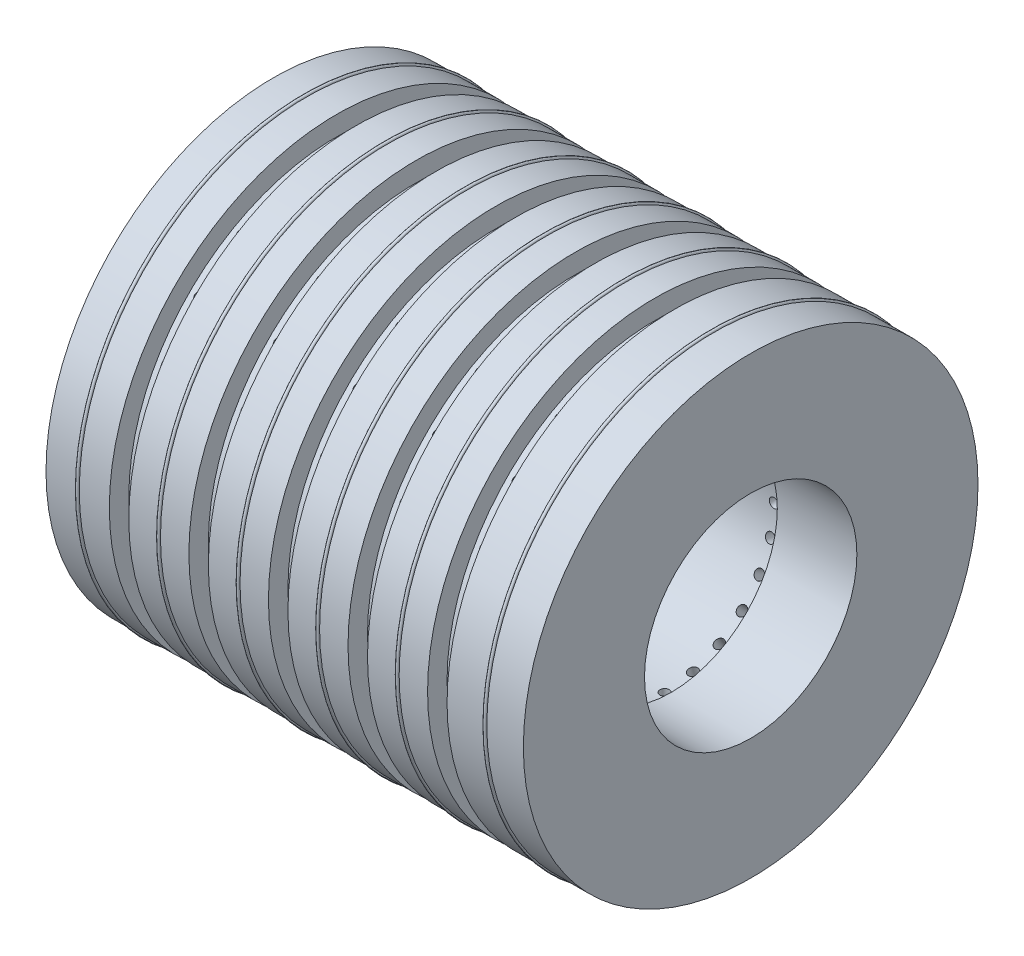
SolidWorks part; units mm, degrees
ref_plane "Front Plane" through (0, 0, 0) normal (0, 0, 1) x (1, 0, 0)
ref_plane "Top Plane" through (0, 0, 0) normal (0, 1, 0) x (1, 0, 0)
ref_plane "Right Plane" through (0, 0, 0) normal (1, 0, 0) x (0, 0, -1)
sketch "Sketch1" plane through (0, 0, 0) normal (0, 0, 1) x (1, 0, 0)
  line L0 (0, 0) -> (36.5459, 0) construction
  line L1 (-6.223, 9.5758) -> (-6.223, 17.78)
  line L3 (31.115, 17.78) -> (31.115, 8.3058)
  line L4 (31.115, 8.3058) -> (24.892, 8.3058)
  line L5 (24.892, 8.3058) -> (24.892, 8.5598)
  line L6 (24.892, 8.5598) -> (18.669, 8.5598)
  line L7 (18.669, 8.5598) -> (18.669, 8.8138)
  line L8 (18.669, 8.8138) -> (12.446, 8.8138)
  line L9 (12.446, 8.8138) -> (12.446, 9.0678)
  line L10 (12.446, 9.0678) -> (6.223, 9.0678)
  line L11 (6.223, 9.0678) -> (6.223, 9.3218)
  line L12 (6.223, 9.3218) -> (0, 9.3218)
  line L13 (0, 9.3218) -> (0, 9.5758)
  line L14 (0, 9.5758) -> (-6.223, 9.5758)
  line L15 (-6.223, 17.78) -> (-3.8735, 17.78)
  line L16 (-1.27, 17.78) -> (-1.27, 16.256)
  line L17 (-1.27, 16.256) -> (0.254, 16.256)
  line L18 (0.254, 16.256) -> (0.254, 17.78)
  line L19 (0.254, 17.78) -> (2.4765, 17.78)
  line L20 (4.953, 17.78) -> (4.953, 16.256)
  line L21 (4.953, 16.256) -> (6.477, 16.256)
  line L22 (6.477, 16.256) -> (6.477, 17.78)
  line L23 (6.477, 17.78) -> (8.6995, 17.78)
  line L24 (11.176, 17.78) -> (11.176, 16.256)
  line L25 (11.176, 16.256) -> (12.7, 16.256)
  line L26 (12.7, 16.256) -> (12.7, 17.78)
  line L27 (12.7, 17.78) -> (14.9225, 17.78)
  line L28 (17.399, 17.78) -> (17.399, 16.256)
  line L29 (17.399, 16.256) -> (18.923, 16.256)
  line L30 (18.923, 16.256) -> (18.923, 17.78)
  line L31 (18.923, 17.78) -> (21.1455, 17.78)
  line L32 (23.622, 17.78) -> (23.622, 16.256)
  line L33 (23.622, 16.256) -> (25.146, 16.256)
  line L34 (25.146, 16.256) -> (25.146, 17.78)
  line L35 (25.146, 17.78) -> (28.0035, 17.78)
  line L36 (-3.6195, 17.78) -> (-1.27, 17.78)
  line L37 (2.7305, 17.78) -> (4.953, 17.78)
  line L38 (8.9535, 17.78) -> (11.176, 17.78)
  line L39 (15.1765, 17.78) -> (17.399, 17.78)
  line L40 (21.3995, 17.78) -> (23.622, 17.78)
  line L41 (28.2575, 17.78) -> (31.115, 17.78)
  line L42 (-3.8735, 17.78) -> (-3.6195, 17.78) construction
  line L43 (2.4765, 17.78) -> (2.7305, 17.78) construction
  line L44 (8.6995, 17.78) -> (8.9535, 17.78) construction
  line L45 (14.9225, 17.78) -> (15.1765, 17.78) construction
  line L46 (21.1455, 17.78) -> (21.3995, 17.78) construction
  line L47 (28.0035, 17.78) -> (28.2575, 17.78) construction
  arc A9 (21.3995, 17.78) -> (21.1455, 17.78) centre (21.2725, 17.78) ccw
  arc A10 (15.1765, 17.78) -> (14.9225, 17.78) centre (15.0495, 17.78) ccw
  arc A11 (8.9535, 17.78) -> (8.6995, 17.78) centre (8.8265, 17.78) ccw
  arc A12 (2.7305, 17.78) -> (2.4765, 17.78) centre (2.6035, 17.78) ccw
  arc A13 (-3.6195, 17.78) -> (-3.8735, 17.78) centre (-3.7465, 17.78) ccw
  arc A14 (28.2575, 17.78) -> (28.0035, 17.78) centre (28.1305, 17.78) ccw
  point P37 (-6.223, 13.6779)
  dimension "D13" = 0.254
  dimension "D2" = 0.254
  dimension "D4" = 17.78
  dimension "D5" = 1.524
  dimension "D6" = 1.524
  dimension "D8" = 1.524
  dimension "D9" = 1.524
  dimension "D10" = 1.524
  dimension "D11" = 1.524
  dimension "D3" = 6.223
  dimension "D12" = 37.338
  dimension "D14" = 9.5758
  dimension "D7" = 0.254
  dimension "D15" = 0.254
  dimension "D16" = 0.254
  dimension "D17" = 0.254
  dimension "D18" = 0.254
revolve "Revolve1" add sketch "Sketch1" angle 360 about L0
ref_plane "Plane1" through (-0.508, 0, 0) normal (-1, 0, 0) x (0, 0, 1)
ref_plane "Plane2" through (5.715, 0, 0) normal (-1, 0, 0) x (0, 0, 1)
ref_plane "Plane3" through (11.938, 0, 0) normal (1, 0, 0) x (0, 0, -1)
ref_plane "Plane4" through (18.161, 0, 0) normal (-1, 0, 0) x (0, 0, 1)
ref_plane "Plane5" through (24.384, 0, 0) normal (1, 0, 0) x (0, 0, -1)
ref_plane "Plane6" through (0, 17.78, 0) normal (0, 1, 0) x (1, 0, 0)
ref_axis "Axis1" through (0, 0, 0) along (-1, 0, 0)
sketch "Sketch4" plane through (-0.508, 0, 0) normal (-1, 0, 0) x (0, 0, 1)
  point P0 (0, 0)
sketch "Sketch5" plane through (5.715, 0, 0) normal (-1, 0, 0) x (0, 0, 1)
  point P0 (0, 0)
sketch "Sketch6" plane through (11.938, 0, 0) normal (1, 0, 0) x (0, 0, -1)
  point P0 (0, 0)
sketch "Sketch7" plane through (18.161, 0, 0) normal (-1, 0, 0) x (0, 0, 1)
  point P0 (0, 0)
sketch "Sketch8" plane through (24.384, 0, 0) normal (1, 0, 0) x (0, 0, -1)
  point P0 (0, 0)
sketch "Sketch9" plane through (0, 17.78, 0) normal (0, 1, 0) x (1, 0, 0)
  point P0 (24.384, 0)
  point P2 (18.161, 0)
  point P4 (11.938, 0)
  point P6 (5.715, 0)
  point P11 (-0.508, 0)
hole_wizard "#69 (0.0292) Diameter Hole1" positions "Sketch9" profile "Sketch10" hole size "#69" standard "ANSI Inch" end condition up to next
sketch "Sketch10" plane through (24.384, 17.78, 0) normal (1, 0, 0) x (0, 0, 1)
  line L0 (0, 0) -> (0, 9.2202)
  line L1 (0, 9.2202) -> (0.3708, 9.2202)
  line L2 (0.3708, 9.2202) -> (0.3708, 0)
  line L5 (0.3708, 0) -> (0, 0)
  line L11 (0, -6.35) -> (0, 107.95) construction
  dimension "Thru Hole Dia." = 0.7417
  dimension "Thru Hole Depth" = 9.2202
pattern_circular "CirPattern1" count 24 every 15 about axis through (0, 0, 0) along (-1, 0, 0) of "#69 (0.0292) Diameter Hole1"
equation "\"kero_radius\"=0.23622in"
equation "\"lox_radius\"=0.23622in"
equation "\"Cavity_width\"=0.031in"
equation "\"tooth_width\"=0.01in"
equation "\"cavity_depth\"=0.031in"
equation "\"seal_step\"=0.01in"
equation "\"purge_length\"=0.04in"
equation "\"D2@Sketch1\"=\"seal_step\""
equation "\"insert_radius\" = 0.7in"
equation "\"recycle_groove width\" = 0.06in"
equation "\"D5@Sketch1\"=\"recycle_groove width\""
equation "\"recycle_groove_depth\" = 0.06in"
equation "\"D6@Sketch1\"=\"recycle_groove_depth\""
equation "\"N2_purge_width\"= .06in"
equation "\"N2_purge_depth\"= .06in"
equation "\"drain_width\"= .06in"
equation "\"drain_depth\"= .06in"
equation "\"D9@Sketch1\"=\"drain_depth\""
equation "\"D8@Sketch1\"=\"drain_width\""
equation "\"D10@Sketch1\"=\"N2_purge_depth\""
equation "\"D11@Sketch1\"=\"N2_purge_width\""
equation "\"radial_clearance\"= .002in"
equation "\"D3@Sketch1\"=\"tooth_width\"*5+\"Cavity_width\"*5+\"purge_length\""
equation "\"Insert_Length\"= \"D12@Sketch1\""
equation "\"InsertLength\"= 1.47in"
equation "\"D4@Sketch1\"=\"insert_radius\""
equation "\"bumb_radius\"= 0.01"
equation "\"D13@Sketch1\"=\"bumb_radius\""
equation "\"bearing_radius\"= 0.629921"
equation "\"bearing_width\"=0.393701"
equation "\"IPS_flange_width\"= .2in"
equation "\"IPS_flange_radius\" = 2.2in"
equation "\"IPS_LOX_male_radius\"= .9in"
equation "\"IPS_Kero_male_radius\" = .9in"
equation "\"IPS_radius\"= 1.5in"
equation "\"lox_in_radius\"=.375in"
equation "\"D14@Sketch1\"=\"lox_in_radius\"+\"radial_clearance\""
equation "\"D7@Sketch1\"=(\"drain_width\"-\"purge_length\")/2"
equation "\"D15@Sketch1\"=(\"drain_width\"-\"purge_length\")/2"
equation "\"D16@Sketch1\"=(\"drain_width\"-\"purge_length\")/2"
equation "\"D17@Sketch1\"=(\"drain_width\"-\"purge_length\")/2"
equation "\"D18@Sketch1\"=(\"drain_width\"-\"purge_length\")/2"
